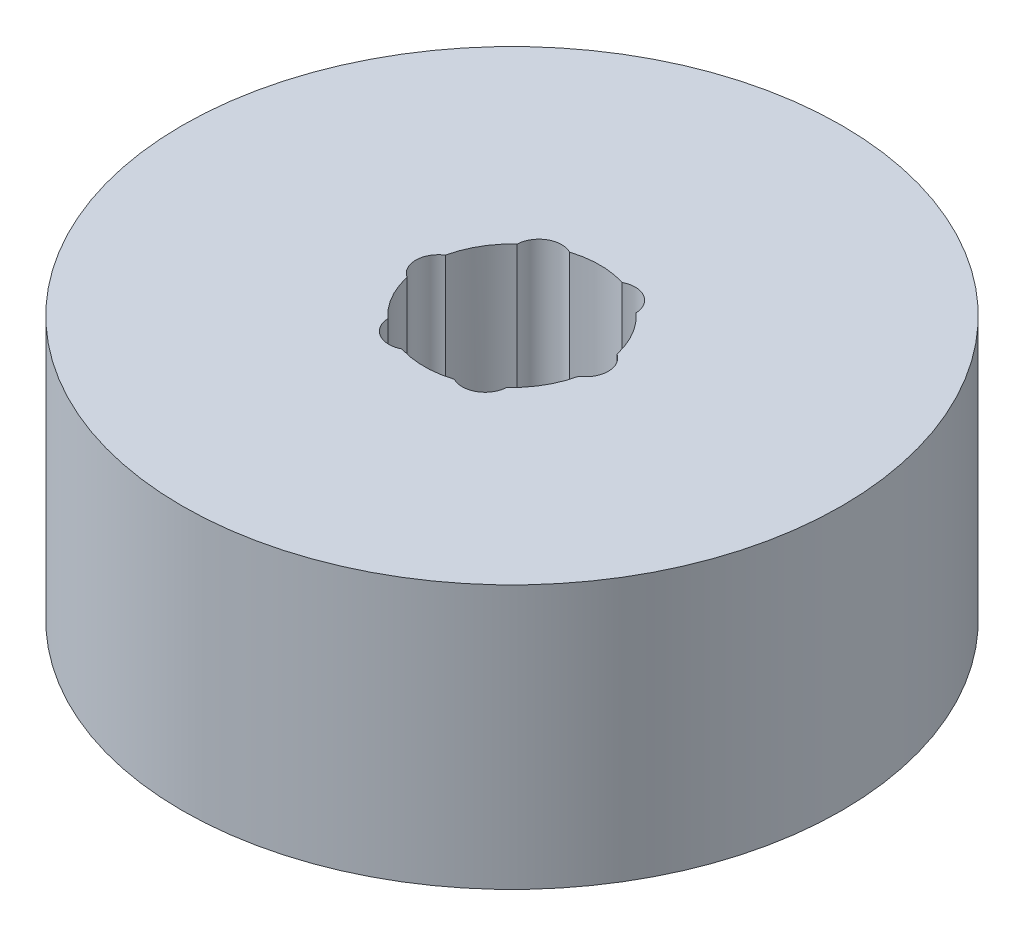
SolidWorks part; units mm, degrees
ref_plane "Front Plane" through (0, 0, 0) normal (0, 0, 1) x (1, 0, 0)
ref_plane "Top Plane" through (0, 0, 0) normal (0, 1, 0) x (1, 0, 0)
ref_plane "Right Plane" through (0, 0, 0) normal (1, 0, 0) x (0, 0, -1)
sketch "Sketch1" plane through (0, 0, 0) normal (0, 1, 0) x (1, 0, 0)
  circle A0 centre (0, 0) radius 37.5
  dimension "FLANGE_OD" = 75
extrude "Boss-Extrude1" add sketch "Sketch1" along normal blind 30
sketch "Sketch2" plane through (0, 0, 0) normal (0, 1, 0) x (1, 0, 0)
  circle A0 centre (0, 0) radius 10
  dimension "BORE_D" = 20
extrude "Cut-Extrude1" cut sketch "Sketch2" along normal through all
sketch "Sketch3" plane through (0, 30, 0) normal (0, 1, 0) x (1, 0, 0)
  circle A0 centre (0, 0) radius 8.3659 construction
  circle A1 centre (-8.3659, 0) radius 2.587
  dimension "BOLT_D" = 5.1739
  dimension "BOLT_PCD" = 16.7318
extrude "Cut-Extrude2" cut sketch "Sketch3" against normal blind 20.8547
pattern_circular "CirPattern1" count 6 over 360 about axis through (0, 0, 0) along (0, 1, 0) of "Cut-Extrude2"
